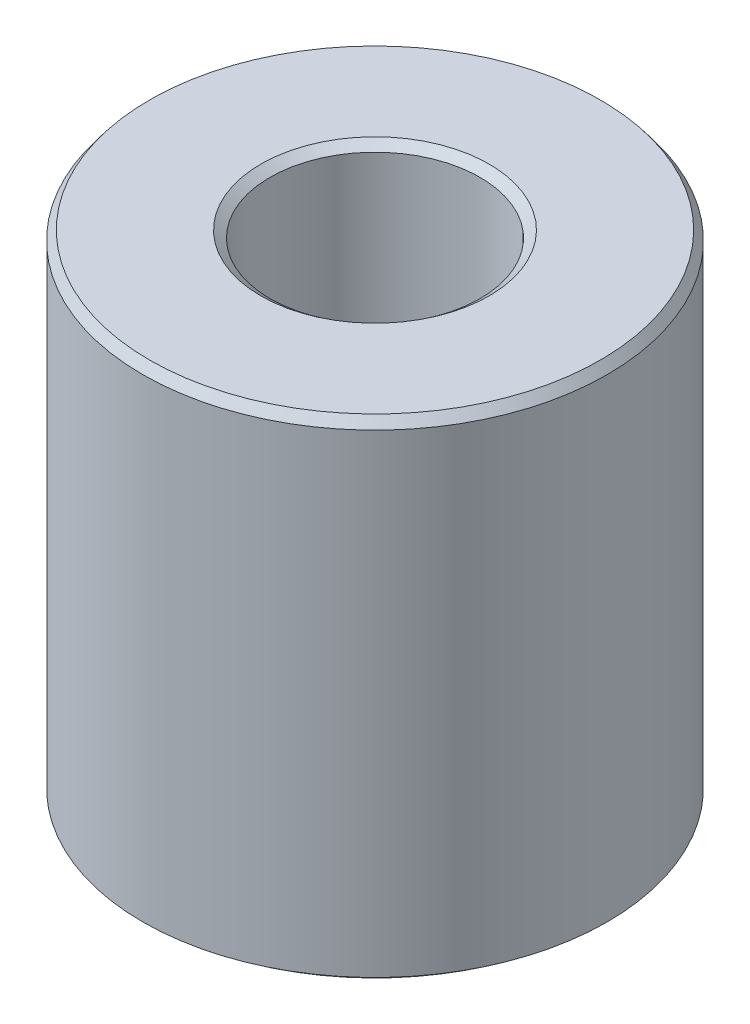
SolidWorks part; units mm, degrees
ref_plane "Front Plane" through (0, 0, 0) normal (0, 0, 1) x (1, 0, 0)
ref_plane "Top Plane" through (0, 0, 0) normal (0, 1, 0) x (1, 0, 0)
ref_plane "Right Plane" through (0, 0, 0) normal (1, 0, 0) x (0, 0, -1)
sketch "Sketch1" plane through (0, 0, 0) normal (0, 1, 0) x (1, 0, 0)
  circle A0 centre (0, 0) radius 57.5
  dimension "SLEEVE_OD" = 115
extrude "Boss-Extrude1" add sketch "Sketch1" along normal blind 121.3149
sketch "Sketch2" plane through (0, 0, 0) normal (0, 1, 0) x (1, 0, 0)
  circle A0 centre (0, 0) radius 26.0103
  dimension "BORE_D" = 52.0206
extrude "Cut-Extrude1" cut sketch "Sketch2" along normal through all
chamfer "Chamfer1" distance 2.2587 angle 37.132 4 edges at (0, 121.3149, 26.0103) (0, 0, 26.0103) (0, 0, 57.5) (0, 121.3149, 57.5) first distance on face at (0, 121.3149, 26.0103) first distance on face at (0, 0, 26.0103) first distance on face at (0, 121.3149, 57.5)
